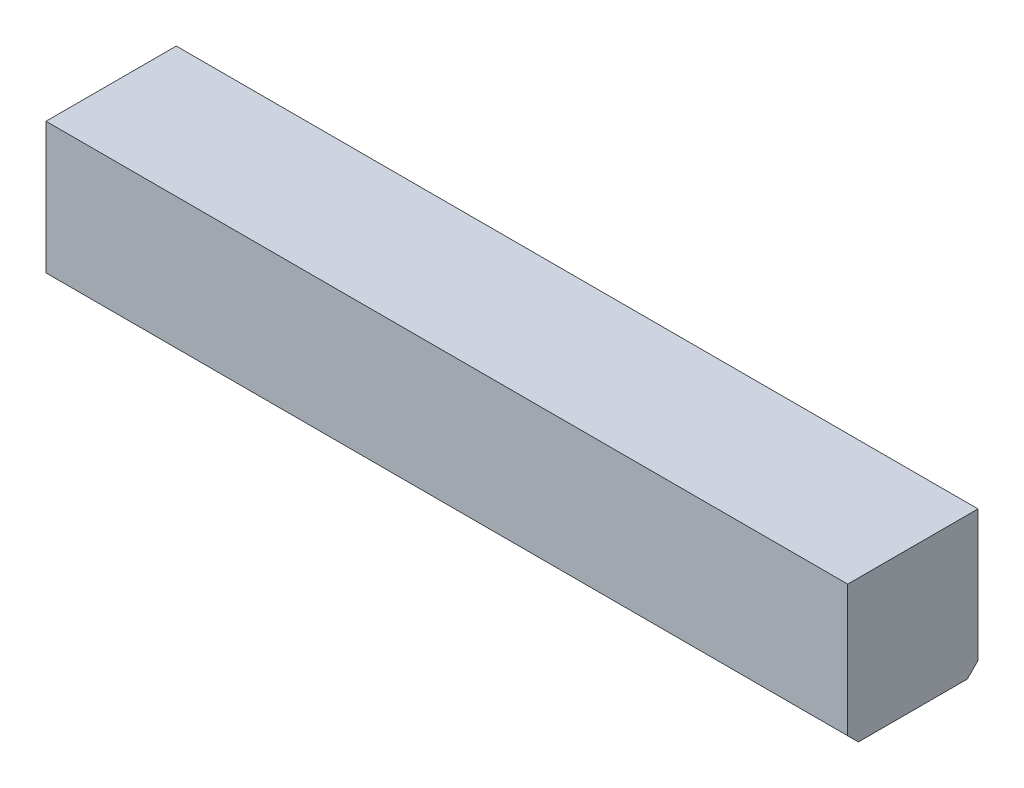
SolidWorks part; units mm, degrees
ref_plane "Front Plane" through (0, 0, 0) normal (0, 0, 1) x (1, 0, 0)
ref_plane "Top Plane" through (0, 0, 0) normal (0, 1, 0) x (1, 0, 0)
ref_plane "Right Plane" through (0, 0, 0) normal (1, 0, 0) x (0, 0, -1)
ref_plane "PX 30.000" through (30, 0, 0) normal (1, 0, 0) x (0, 0, -1)
sketch "spacer sketch" plane through (30, 0, 0) normal (1, 0, 0) x (0, 0, -1)
  line L0 (-0.8, 0) -> (0, 0.8)
  line L1 (0, 0.8) -> (0, 10.63)
  line L2 (0, 10.63) -> (-9.75, 10.63)
  line L3 (-9.75, 10.63) -> (-9.75, 0.8)
  line L4 (-9.75, 0.8) -> (-8.95, 0)
  line L5 (-8.95, 0) -> (-0.8, 0)
extrude "spacer" add sketch "spacer sketch" along normal mid plane 60
equation "\"diffL\" = 608.8mm"
equation "\"diffW\" = 329.4mm"
equation "\"diffT\" = 2.9mm"
equation "\"chanSlotW\" = 12.9mm"
equation "\"chanSlotDepth\" = 11.13mm"
equation "\"chanFloor\" = 1.57mm"
equation "\"chanLeg\" = 12.7mm"
equation "\"lightL\" = 604.8mm"
equation "\"lightW\" = 330.2mm"
equation "\"lightH\" = 92mm"
equation "\"lightSideFlat\" = 30mm"
equation "\"lightSlopeLen\" = 38.9mm"
equation "\"lightWingDepth\" = 50.1mm"
equation "\"lightWingFlat\" = 90.2mm"
equation "\"lightChanW\" = 99.6mm"
equation "\"lightChanStand\" = 44.1mm"
equation "\"insFlangeD\" = 12.3mm"
equation "\"insFromEnd\" = 20.7mm"
equation "\"insUpSlope\" = 20.8mm"
equation "\"gaugeH\" = 10mm"
equation "\"gaugeStepLen\" = 14mm"
equation "\"gaugeStepW0\" = 13.1mm"
equation "\"gaugeStepDW\" = 0.2mm"
equation "\"gaugeSteps\" = 5mm"
equation "\"gaugeHandleLen\" = 30mm"
equation "\"gaugeHandleW\" = 24mm"
equation "\"gaugeSlot0\" = 3mm"
equation "\"gaugeSlotD\" = 0.1mm"
equation "\"gaugeSlotDepth\" = 8mm"
equation "\"gap\" = 25.4mm"
equation "\"edgeL\" = 1mm"
equation "\"edgeW\" = 0.75mm"
equation "\"proud\" = 1.5mm"
equation "\"seatClr\" = 0.15mm"
equation "\"tongueClrZ\" = 0.1mm"
equation "\"tongueClrX\" = 0.25mm"
equation "\"tongueLen\" = 30mm"
equation "\"armSide\" = 45mm"
equation "\"armEnd\" = 20mm"
equation "\"cornerCham\" = 3mm"
equation "\"brkW\" = 26mm"
equation "\"brkT\" = 7mm"
equation "\"brkSeatClr\" = 0.3mm"
equation "\"brkScrewSpan\" = 16mm"
equation "\"pilotD\" = 2.7mm"
equation "\"pilotDepth\" = 10mm"
equation "\"screwClrD\" = 3.9mm"
equation "\"jogBelow\" = 4mm"
equation "\"padT\" = 7mm"
equation "\"padLen\" = 36mm"
equation "\"m6Clr\" = 7mm"
equation "\"m6Slot\" = 6mm"
equation "\"flangeRelD\" = 17mm"
equation "\"flangeRelDepth\" = 1.5mm"
equation "\"relLen\" = 5mm"
equation "\"relDepth\" = 3.3mm"
equation "\"knockN\" = 100mm"
equation "\"petgcfE\" = 3000mm"
equation "\"mockExtent\" = 110mm"
equation "\"relZnear\" = 9.4mm"
equation "\"relZfar\" = 23.4mm"
equation "\"headD\" = 8mm"
equation "\"headH\" = 2.5mm"
equation "\"headFromEnd\" = 6.8mm"
equation "\"headBack\" = 16.4mm"
equation "\"sideClr\" = 0.4mm"
equation "\"cornerRelR\" = 1.5mm"
equation "\"cornerRelBack\" = 0.6mm"
equation "\"endHeadH\" = 2.8mm"
equation "\"footClr\" = 1.2mm"
equation "\"footEndClr\" = 3.5mm"
equation "\"footLift\" = 6mm"
equation "\"footBlockClr\" = 0.5mm"
equation "\"footBack\" = 50mm"
equation "\"footFwd\" = 10mm"
equation "\"footRibH\" = 16mm"
equation "\"footRibT\" = 6mm"
equation "\"footBraceEnd\" = 3mm"
equation "\"footLoadN\" = 25mm"
equation "\"spacerLen\" = 60mm"
equation "\"spacerShort\" = 0.5mm"
equation "\"spacerCham\" = 0.8mm"
equation "\"spacerPerSide\" = 3mm"
equation "\"spacerPerEnd\" = 1mm"
equation "\"toolR\" = 9mm"
equation "\"visR\" = 4mm"
equation "\"edgeR\" = 1mm"
equation "\"bendOutR\" = 5mm"
equation "\"insideR\" = 2.5mm"
equation "\"footCornerR\" = 10mm"
equation "\"footFrontR\" = 8mm"
equation "\"braceKinkR\" = 12mm"
equation "\"bedCham\" = 1mm"
equation "\"bedChamSmall\" = 0.6mm"
equation "\"soleTopR\" = 2mm"
equation "\"cornerR\" = 6mm"
equation "\"rimInR\" = 1mm"
equation "\"insFlangeH\" = 1mm"
